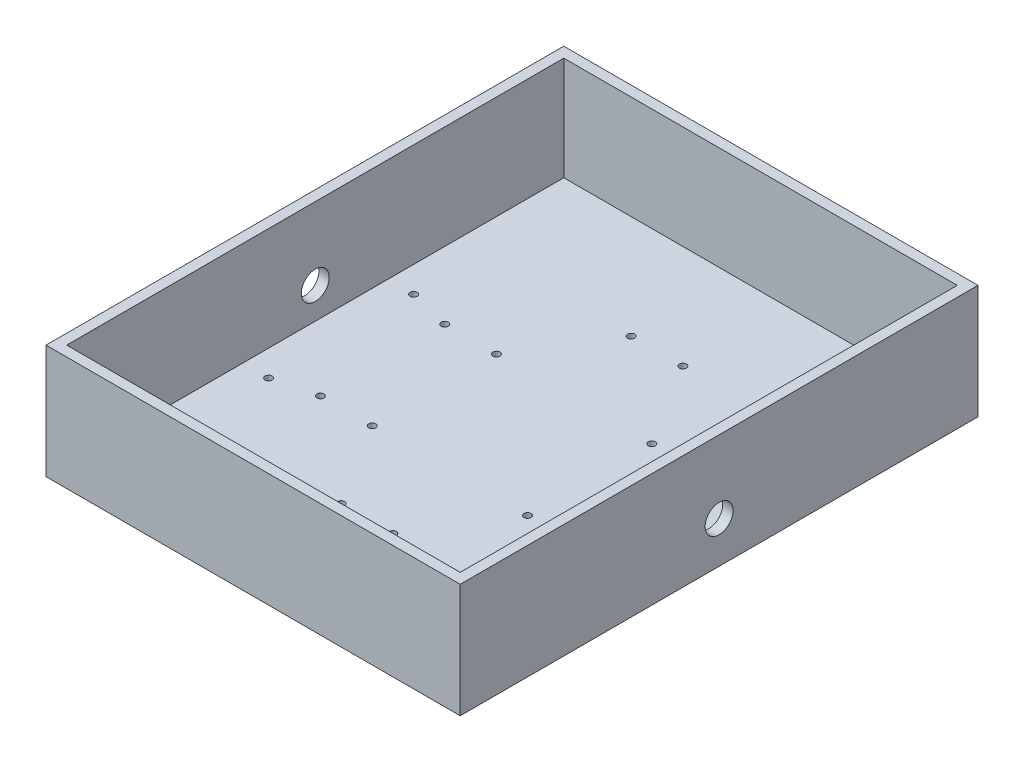
SolidWorks part; units mm, degrees
ref_plane "Front Plane" through (0, 0, 0) normal (0, 0, 1) x (1, 0, 0)
ref_plane "Top Plane" through (0, 0, 0) normal (0, 1, 0) x (1, 0, 0)
ref_plane "Right Plane" through (0, 0, 0) normal (1, 0, 0) x (0, 0, -1)
sketch "Sketch1" plane through (0, 0, 0) normal (0, 0, 1) x (1, 0, 0)
  line L0 (0, 50) -> (0, 0) construction
  line L1 (-95, 0) -> (95, 0)
  line L2 (-95, 0) -> (-95, 50)
  line L3 (-95, 50) -> (95, 50)
  line L4 (95, 0) -> (95, 50)
  dimension "D1" = 190
  dimension "D2" = 50
extrude "Boss-Extrude1" add sketch "Sketch1" along normal mid plane 240
shell "Shell1" thickness 5 removed face at (0, 50, 0) outward yes
sketch "Sketch2" plane through (0, 0, 0) normal (0, 1, 0) x (1, 0, 0)
  line L0 (-26.87, 0) -> (34.5029, 0) construction
  line L1 (0, -20.877) -> (0, 39.4378) construction
  circle A12 centre (-12.5, 70) radius 1.7
  circle A13 centre (-37.5, 30) radius 1.7
  circle A14 centre (-62.5, 30) radius 1.7
  circle A15 centre (-82.5, 35) radius 1.7
  circle A28 centre (82.5, 35) radius 1.7
  circle A29 centre (62.5, 30) radius 1.7
  circle A30 centre (37.5, 30) radius 1.7
  circle A31 centre (12.5, 70) radius 1.7
  circle A32 centre (12.5, -70) radius 1.7
  circle A33 centre (37.5, -30) radius 1.7
  circle A34 centre (62.5, -30) radius 1.7
  circle A35 centre (82.5, -35) radius 1.7
  circle A36 centre (-82.5, -35) radius 1.7
  circle A37 centre (-62.5, -30) radius 1.7
  circle A38 centre (-37.5, -30) radius 1.7
  circle A39 centre (-12.5, -70) radius 1.7
  point P3 (0, 0)
  dimension "D8" = 3.4
  dimension "D1" = 25
  dimension "D2" = 20
  dimension "D3" = 5
  dimension "D4" = 40
  dimension "D5" = 30
  dimension "D6" = 25
  dimension "D7" = 12.5
extrude "Cut-Extrude1" cut sketch "Sketch2" against normal through all both and the other way through all
sketch "Sketch3" plane through (0, 0, 0) normal (1, 0, 0) x (0, 0, -1)
  line L0 (-125, -5) -> (125, -5) construction
  circle A0 centre (0, 15) radius 6.75
  dimension "D2" = 13.5
  dimension "D1" = 20
extrude "Cut-Extrude2" cut sketch "Sketch3" against normal through all both and the other way through all
